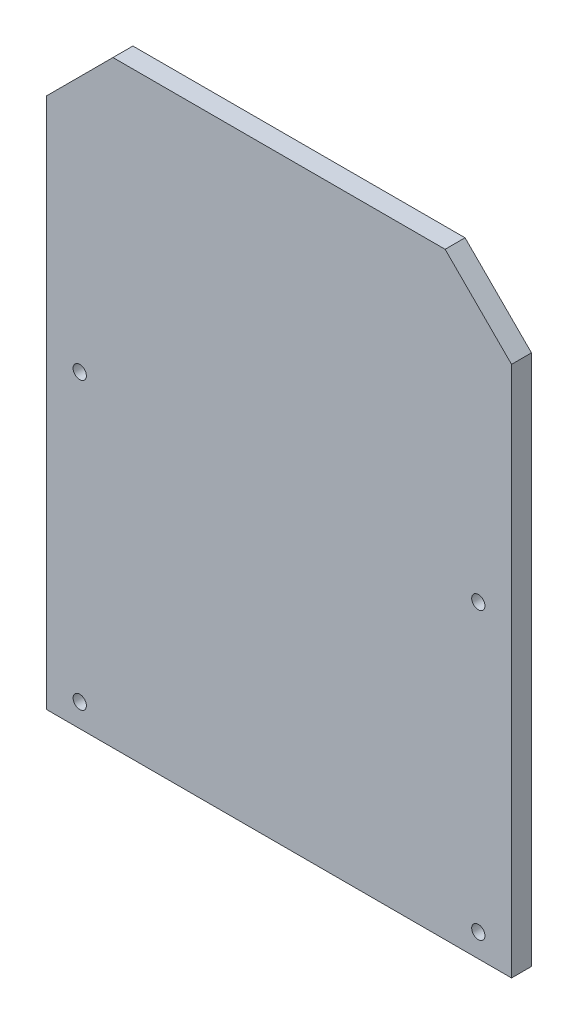
SolidWorks part; units mm, degrees
ref_plane "Alzado" through (0, 0, 0) normal (0, 0, 1) x (1, 0, 0)
ref_plane "Planta" through (0, 0, 0) normal (0, 1, 0) x (1, 0, 0)
ref_plane "Vista lateral" through (0, 0, 0) normal (1, 0, 0) x (0, 0, -1)
sketch "Croquis1" plane through (0, 0, 0) normal (0, 0, 1) x (1, 0, 0)
  line L5 (-30.0455, 36.9284) -> (39.9545, 36.9284)
  line L6 (-30.0455, 36.9284) -> (-30.0455, -53.0716)
  line L7 (-30.0455, -53.0716) -> (39.9545, -53.0716)
  line L8 (39.9545, 36.9284) -> (39.9545, -53.0716)
  dimension "D1" = 70
  dimension "D2" = 90
extrude "Saliente-Extruir1" add sketch "Croquis1" along normal blind 3
sketch "Croquis2" plane through (0, 0, 0) normal (0, 0, -1) x (-1, 0, 0)
  line L0 (-34.9545, -49.5716) -> (-39.9545, -49.5716) construction
  line L1 (-39.9545, -53.0716) -> (-39.9545, 36.9284) construction
  line L2 (25.0455, -49.5716) -> (30.0455, -49.5716) construction
  line L3 (30.0455, 36.9284) -> (30.0455, -53.0716) construction
  line L4 (25.0455, -49.5716) -> (25.0455, -53.0716) construction
  line L5 (30.0455, -53.0716) -> (-39.9545, -53.0716) construction
  line L6 (-34.9545, -49.5716) -> (-34.9545, -53.0716) construction
  line L7 (-34.9545, -6.5716) -> (-34.9545, -49.5716) construction
  circle A0 centre (-34.9545, -49.5716) radius 1
  circle A1 centre (25.0455, -49.5716) radius 1
  circle A2 centre (-34.9545, -6.5716) radius 1
  circle A3 centre (25.0455, -6.5716) radius 1
extrude "Cortar-Extruir1" cut sketch "Croquis2" against normal blind 3
sketch "Croquis3" plane through (0, 0, 0) normal (0, 0, -1) x (-1, 0, 0)
  line L1 (-39.9545, 36.9284) -> (30.0455, 36.9284) construction
  line L3 (-39.9545, -53.0716) -> (-39.9545, 36.9284) construction
  line L5 (-39.9545, 36.9284) -> (30.0455, 36.9284)
  line L6 (-39.9545, -53.0716) -> (-39.9545, 36.9284)
fillet "Chaflán1" radius 10 1 edges at (39.9545, 36.9284, 1.5) type face fillet profile chamfer first side face at (39.9545, -8.0716, 1.5) second side face at (4.9545, 36.9284, 1.5)
fillet "Chaflán2" radius 10 1 edges at (-30.0455, 36.9284, 1.5) type face fillet profile chamfer first side face at (-0.0455, 36.9284, 1.5) second side face at (-30.0455, -8.0716, 1.5)
